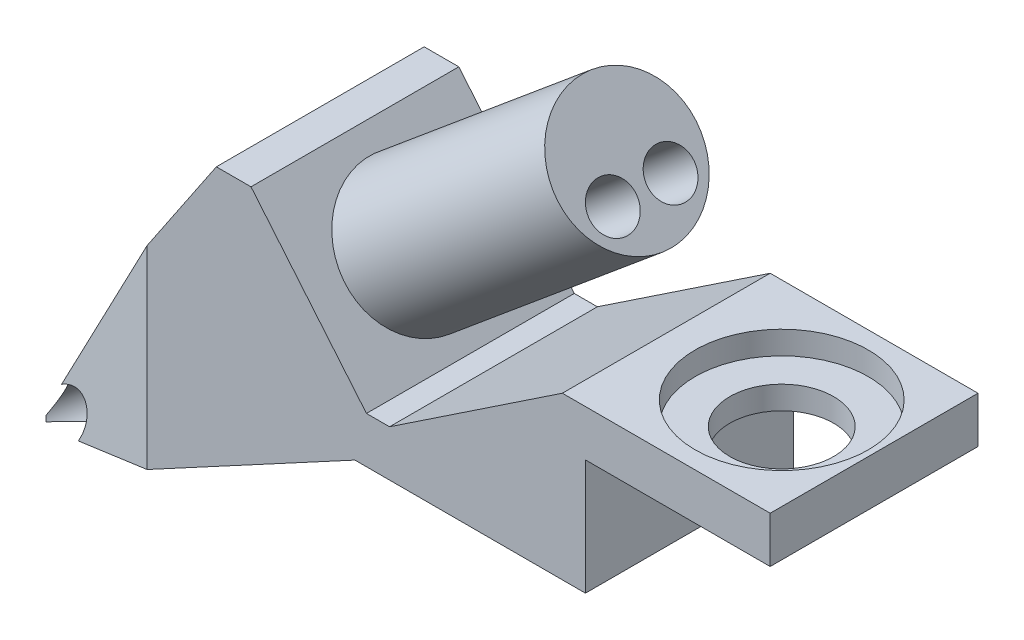
SolidWorks part; units mm, degrees
ref_plane "Front Plane" through (0, 0, 0) normal (0, 0, 1) x (1, 0, 0)
ref_plane "Top Plane" through (0, 0, 0) normal (0, 1, 0) x (1, 0, 0)
ref_plane "Right Plane" through (0, 0, 0) normal (1, 0, 0) x (0, 0, -1)
sketch "Sketch1" plane through (0, 0, 0) normal (0, 0, 1) x (1, 0, 0)
  line L0 (0, 0) -> (17.6167, 9.5)
  line L1 (17.6167, 9.5) -> (27.6, 9.5)
  line L2 (27.6, 9.5) -> (27.6, 14.5)
  line L3 (27.6, 14.5) -> (35.6, 14.5)
  line L4 (35.6, 14.5) -> (35.6, 16.5)
  line L5 (35.6, 16.5) -> (26.6, 16.5)
  line L8 (11.6167, 17.5) -> (0, 0.25)
  line L10 (18.1167, 11.5) -> (13.1167, 17.5)
  line L11 (13.1167, 17.5) -> (11.6167, 17.5)
  line L12 (26.6, 16.5) -> (19.1167, 11.5)
  line L13 (19.1167, 11.5) -> (18.1167, 11.5)
  line L14 (0, 0) -> (0, 0.25)
  dimension "D1" = 35.6
  dimension "D2" = 9.5
  dimension "D3" = 14.5
  dimension "D4" = 17.5
  dimension "D5" = 2
  dimension "D6" = 8
  dimension "D7" = 2
  dimension "D8" = 1.5
  dimension "D9" = 0.5
  dimension "D10" = 1
  dimension "D11" = 1
  dimension "D12" = 5
  dimension "D13" = 9
  dimension "D14" = 0.25
extrude "Boss-Extrude1" add sketch "Sketch1" along normal blind 9
sketch "Sketch2" plane through (0, 16.5, 0) normal (0, 1, 0) x (1, 0, 0)
  line L0 (35.6, -9) -> (35.6, 0) construction
  line L1 (8.6167, 0) -> (0, 0)
  line L2 (0, 0) -> (0, -4)
  line L3 (0, -4) -> (8.6167, 0)
  line L4 (0, -5) -> (0, -9)
  line L5 (0, -9) -> (8.6167, -9)
  line L6 (0, -9) -> (0, 0) construction
  line L7 (11.6167, 0) -> (0, 0) construction
  line L8 (0, -5) -> (8.6167, -9)
  line L9 (11.6167, -9) -> (0, -9) construction
  line L10 (11.6167, -9) -> (11.6167, 0) construction
  circle A0 centre (31.6, -4.5) radius 2.25
  circle A1 centre (31.6, -4.5) radius 3.75
  point P5 (35.6, -4.5)
  point P19 (0, -4.5)
  dimension "D3" = 4.5
  dimension "D5" = 7.5
  dimension "D1" = 4
  dimension "D2" = 1
  dimension "D4" = 3
  dimension "D6" = 0.5
extrude "Cut-Extrude1" cut sketch "Sketch2" against normal up to vertex (16.5 mm away) contours A0 | L2 L3 L1 | L8 L4 L5 region at (2.8722, 16.5, 1.3333) region at (2.8722, 16.5, 7.6667) region at (31.6, 16.5, 4.5) up to point (0, 0, 9)
extrude "Cut-Extrude2" cut sketch "Sketch2<3>" against normal blind 1 contours A1 A0 region at (27.9561, 16.5, 4.5)
sketch "Sketch2<3>" plane through (0, 16.5, 0) normal (0, 1, 0) x (1, 0, 0) same geometry as "Sketch2"
sketch "Sketch3" plane through (16.3476, 13.623, 0) normal (0.7682, 0.6402, 0) x (0, 0, -1)
  line L0 (-9, 5.0468) -> (0, 5.0468) construction
  circle A0 centre (-4.5, 1.0468) radius 3
  point P4 (-4.5, 5.0468)
  dimension "D1" = 6
  dimension "D2" = 4
extrude "Boss-Extrude2" add sketch "Sketch3" along normal blind 12
sketch "Sketch4" plane through (16.3476, 13.623, 0) normal (0.7682, 0.6402, 0) x (0, 0, -1)
  line L0 (-5.75, 0.0468) -> (-3.25, 0.0468) construction
  line L1 (-4.5, 4.0468) -> (-4.5, -1.9532) construction
  line L2 (-7.5, 1.0468) -> (-1.5, 1.0468) construction
  circle A0 centre (-5.75, 0.0468) radius 1
  circle A1 centre (-3.25, 0.0468) radius 1
  circle A2 centre (-4.5, 1.0468) radius 3 construction
  circle A3 centre (-4.5, 1.0468) radius 3 construction
  point P13 (-4.5, 0.0468)
  point P14 (-3.75, 1.0468)
  point P15 (-5.0916, 0.1697)
  dimension "D1" = 2
  dimension "D2" = 2.5
  dimension "D3" = 1
extrude "Cut-Extrude3" cut sketch "Sketch4" against normal through all both and the other way through all
equation "\"D6@Sketch2\"=\"D2@Sketch2\"/2"
